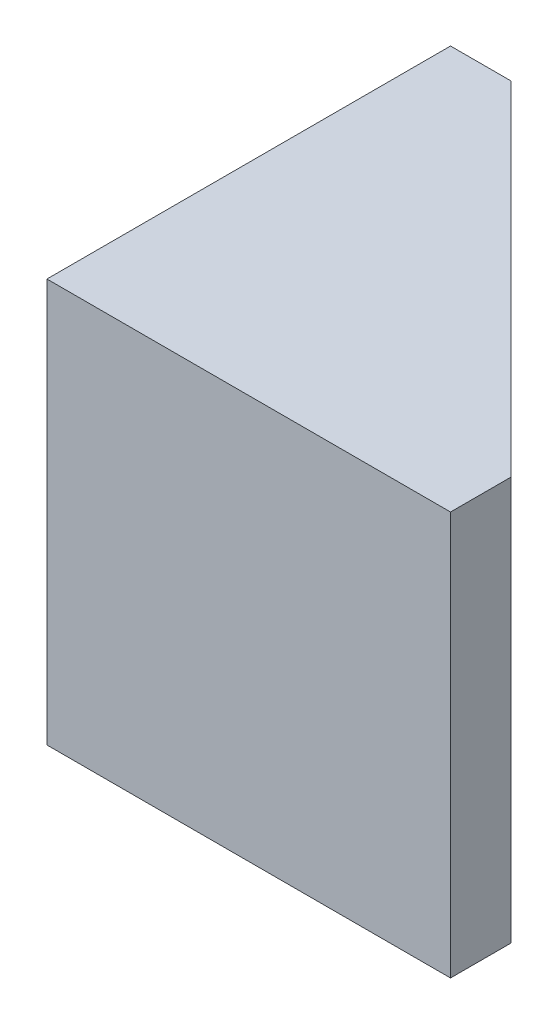
SolidWorks part; units mm, degrees
ref_plane "Спереди" through (0, 0, 0) normal (0, 0, 1) x (1, 0, 0)
ref_plane "Сверху" through (0, 0, 0) normal (0, 1, 0) x (1, 0, 0)
ref_plane "Справа" through (0, 0, 0) normal (1, 0, 0) x (0, 0, -1)
sketch "Эскиз1" plane through (0, 0, 0) normal (0, 1, 0) x (1, 0, 0)
  line L0 (0, 0) -> (0, 20)
  line L1 (0, 20) -> (3, 20)
  line L2 (3, 20) -> (3, 3)
  line L3 (3, 3) -> (20, 3)
  line L4 (20, 3) -> (20, 0)
  line L5 (20, 0) -> (0, 0)
  line L6 (3, 20) -> (20, 3)
  dimension "D1" = 20
  dimension "D2" = 3
extrude "Бобышка-Вытянуть1" add sketch "Эскиз1" along normal mid plane 20 contours L5 L4 L3 L2 L1 L0 region at (0.2828, 0, -10)
extrude "Бобышка-Вытянуть2" add sketch "Эскиз1<3>" along normal blind 3 from offset 10 contours L6 L2 L3 region at (8.6667, 0, -8.6667) offset against normal yes
sketch "Эскиз1<3>" plane through (0, 0, 0) normal (0, 1, 0) x (1, 0, 0) same geometry as "Эскиз1"
mirror "Зеркальное отражение2" about plane through (0, 0, 0) normal (0, 1, 0) of "Бобышка-Вытянуть2"
